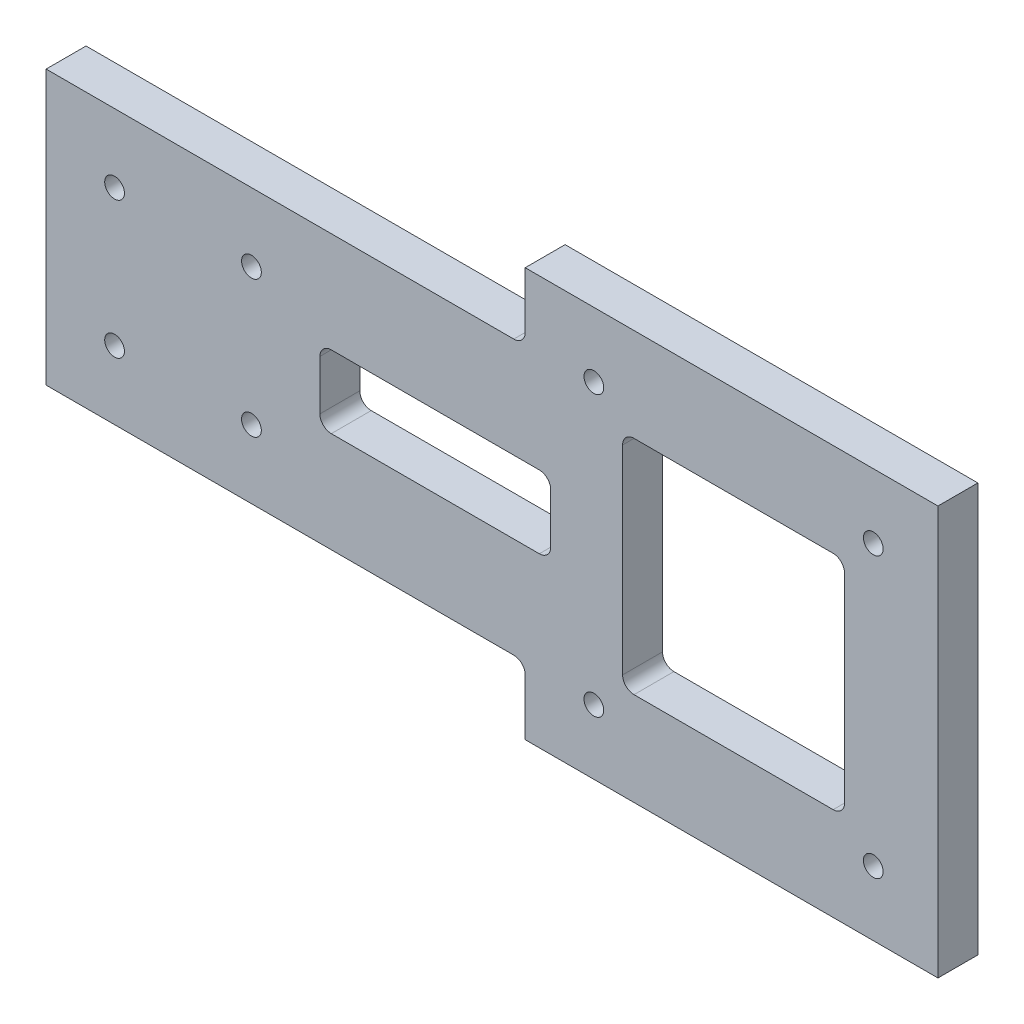
SolidWorks part; units mm, degrees
material "6061-T6 (SS)"
ref_plane "Front" through (0, 0, 0) normal (0, 0, 1) x (1, 0, 0)
ref_plane "Top" through (0, 0, 0) normal (0, 1, 0) x (1, 0, 0)
ref_plane "Right" through (0, 0, 0) normal (1, 0, 0) x (0, 0, -1)
sketch "Sketch1" plane through (0, 0, 0) normal (0, 0, 1) x (1, 0, 0)
  line L0 (95.25, 38.1) -> (95.25, 56.8909)
  line L1 (95.25, 38.1) -> (-38.1, 38.1)
  line L3 (95.25, -38.1) -> (-38.1, -38.1)
  line L4 (-38.1, 38.1) -> (-38.1, -38.1)
  line L5 (-38.1, -38.1) -> (0, 0) construction
  line L6 (0, 0) -> (-38.1, 38.1) construction
  line L7 (95.25, 56.8909) -> (210.1409, 56.8909)
  line L8 (210.1409, 56.8909) -> (210.1409, 30.8909)
  line L9 (210.1409, 30.8909) -> (122.3591, 30.8909)
  line L10 (122.3591, 30.8909) -> (122.3591, -30.8909)
  line L11 (122.3591, -30.8909) -> (210.1409, -30.8909)
  line L12 (210.1409, -30.8909) -> (210.1409, -56.8909)
  line L13 (210.1409, -56.8909) -> (95.25, -56.8909)
  line L14 (95.25, -56.8909) -> (95.25, -38.1)
  line L15 (192.1409, -30.8909) -> (192.1409, -38.8909) construction
  line L16 (192.1409, -38.8909) -> (192.1409, -56.8909) construction
  line L17 (0, 0) -> (153.25, 0) construction
  line L18 (192.1409, -38.8909) -> (114.3591, 38.8909) construction
  line L19 (192.1409, 38.8909) -> (114.3591, -38.8909) construction
  line L20 (122.3591, 30.8909) -> (153.25, 0) construction
  line L21 (153.25, 0) -> (122.3591, -30.8909) construction
  line L22 (192.1409, 38.8909) -> (192.1409, 56.8909) construction
  line L23 (192.1409, 38.8909) -> (210.1409, 38.8909) construction
  line L24 (192.1409, 38.8909) -> (192.1409, 30.8909) construction
  line L25 (114.3591, 38.8909) -> (95.25, 38.8909) construction
  line L26 (0, 0) -> (122.3591, 0) construction
  line L27 (0, 0) -> (95.25, -38.1) construction
  line L28 (0, 0) -> (95.25, 38.1) construction
  line L29 (192.1409, -38.8909) -> (210.1409, -38.8909) construction
  line L30 (153.25, 0) -> (153.25, 30.8909) construction
  line L31 (153.25, 0) -> (122.3591, 0) construction
  circle A0 centre (153.25, 0) radius 55 construction
  point P0 (0, 0)
  point P17 (192.1409, 38.8909)
  point P18 (192.1409, -38.8909)
  point P19 (114.3591, 38.8909)
  point P20 (114.3591, -38.8909)
  dimension "D2" = 110
  dimension "D1" = 76.2
  dimension "D3" = 90
  dimension "D5" = 8
  dimension "D6" = 18
  dimension "D7" = 133.35
  dimension "D9" = 58
  dimension "D10" = 0
extrude "Boss-Extrude1" add sketch "Sketch1" along normal blind 11.1125
hole_wizard "M5 Clearance Hole1" positions "Sketch3" profile "Sketch4" hole size "M5" standard "ANSI Metric"
sketch "Sketch3" plane through (0, 0, 11.1125) normal (0, 0, 1) x (1, 0, 0)
  line L0 (0, 0) -> (153.25, 0) construction
  line L2 (192.1409, -38.8909) -> (114.3591, 38.8909) construction
  line L4 (192.1409, 38.8909) -> (114.3591, -38.8909) construction
  line L6 (122.3591, 30.8909) -> (153.25, 0) construction
  line L7 (153.25, 0) -> (122.3591, -30.8909) construction
  line L8 (95.25, 38.1) -> (-38.1, 38.1) construction
  line L12 (95.25, -38.1) -> (95.25, -56.8909) construction
  circle A0 centre (153.25, 0) radius 55 construction
  point P0 (192.1409, 38.8909)
  point P2 (192.1409, -38.8909)
  point P4 (114.3591, 38.8909)
  point P6 (114.3591, -38.8909)
  point P55 (158.2936, 0)
  point P56 (0, 0)
  point P57 (0, 0)
  dimension "D1" = 110
  dimension "D2" = 135
  dimension "D3" = 90
  dimension "D4" = 58
sketch "Sketch4" plane through (192.1409, 38.8909, 11.1125) normal (1, 0, 0) x (0, -1, 0)
  line L0 (0, 0) -> (0, 20.4024)
  line L1 (0, 20.4024) -> (2.75, 18.75)
  line L2 (2.75, 18.75) -> (2.75, 0)
  line L5 (2.75, 0) -> (0, 0)
  line L10 (0, 20.4024) -> (-2.75, 18.75) construction
  line L11 (0, -6.35) -> (0, 107.95) construction
  dimension "Hole Dia." = 5.5
  dimension "Hole Depth" = 18.75
  dimension "Drill Angle" = 118
fillet "Fillet1" radius 3.175 4 edges at (122.3591, 30.8909, 5.5562) (122.3591, -30.8909, 5.5562) (95.25, -38.1, 5.5562) (95.25, 38.1, 5.5562)
hole_wizard "M5 Clearance Hole2" positions "Sketch5" profile "Sketch6" hole size "M5" standard "ANSI Metric"
sketch "Sketch5" plane through (0, 0, 11.1125) normal (0, 0, 1) x (1, 0, 0)
  line L0 (-19.05, 19.05) -> (19.05, 19.05) construction
  line L1 (19.05, 19.05) -> (19.05, -19.05) construction
  line L2 (19.05, -19.05) -> (-19.05, -19.05) construction
  line L3 (-19.05, -19.05) -> (-19.05, 19.05) construction
  line L5 (92.075, 38.1) -> (-38.1, 38.1) construction
  line L9 (-38.1, -38.1) -> (-19.05, -19.05) construction
  line L11 (-19.05, 19.05) -> (-38.1, 38.1) construction
  point P0 (-19.05, 19.05)
  point P2 (19.05, 19.05)
  point P4 (19.05, -19.05)
  point P6 (-19.05, -19.05)
  dimension "D1" = 19.05
  dimension "D2" = 38.1
sketch "Sketch6" plane through (-19.05, 19.05, 11.1125) normal (1, 0, 0) x (0, -1, 0)
  line L0 (0, 0) -> (0, 20.4024)
  line L1 (0, 20.4024) -> (2.75, 18.75)
  line L2 (2.75, 18.75) -> (2.75, 0)
  line L5 (2.75, 0) -> (0, 0)
  line L10 (0, 20.4024) -> (-2.75, 18.75) construction
  line L11 (0, -6.35) -> (0, 107.95) construction
  dimension "Hole Dia." = 5.5
  dimension "Hole Depth" = 18.75
  dimension "Drill Angle" = 118
sketch "Sketch7" plane through (0, 0, 11.1125) normal (0, 0, 1) x (1, 0, 0)
  line L0 (19.05, 19.05) -> (19.05, 38.1) construction
  line L1 (102.3591, -10.1) -> (38.1, -10.1)
  line L2 (102.3591, -10.1) -> (102.3591, 10.1)
  line L3 (102.3591, 10.1) -> (38.1, 10.1)
  line L4 (38.1, -10.1) -> (38.1, 10.1)
  line L5 (102.3591, -10.1) -> (38.1, 10.1) construction
  line L6 (102.3591, 10.1) -> (38.1, -10.1) construction
  line L7 (122.3591, -27.7159) -> (122.3591, 27.7159) construction
  line L8 (92.075, 38.1) -> (-38.1, 38.1) construction
  line L9 (0, 0) -> (70.2296, 0) construction
  line L10 (19.05, 19.05) -> (38.1, 19.05) construction
  point P0 (70.2296, 0)
  dimension "D1" = 20
  dimension "D2" = 28
extrude "Cut-Extrude1" cut sketch "Sketch7" against normal through all
fillet "Fillet2" radius 3.175 4 edges at (102.3591, -10.1, 5.5562) (102.3591, 10.1, 5.5562) (38.1, 10.1, 5.5562) (38.1, -10.1, 5.5562)
sketch "Sketch8" plane through (0, 0, 11.1125) normal (0, 0, 1) x (1, 0, 0)
  line L0 (125.5341, 30.8909) -> (210.1409, 30.8909) construction
  line L1 (210.1409, -30.8909) -> (184.1409, -30.8909)
  line L2 (210.1409, -30.8909) -> (210.1409, 30.8909)
  line L3 (210.1409, 30.8909) -> (184.1409, 30.8909)
  line L4 (184.1409, -30.8909) -> (184.1409, 30.8909)
  line L5 (210.1409, -56.8909) -> (210.1409, -30.8909) construction
extrude "Boss-Extrude2" add sketch "Sketch8" against normal up to surface (11.1125 mm away) up to face at (70.2296, 0, 0)
fillet "Fillet3" radius 3.175 2 edges at (184.1409, -30.8909, 5.5562) (184.1409, 30.8909, 5.5562)
